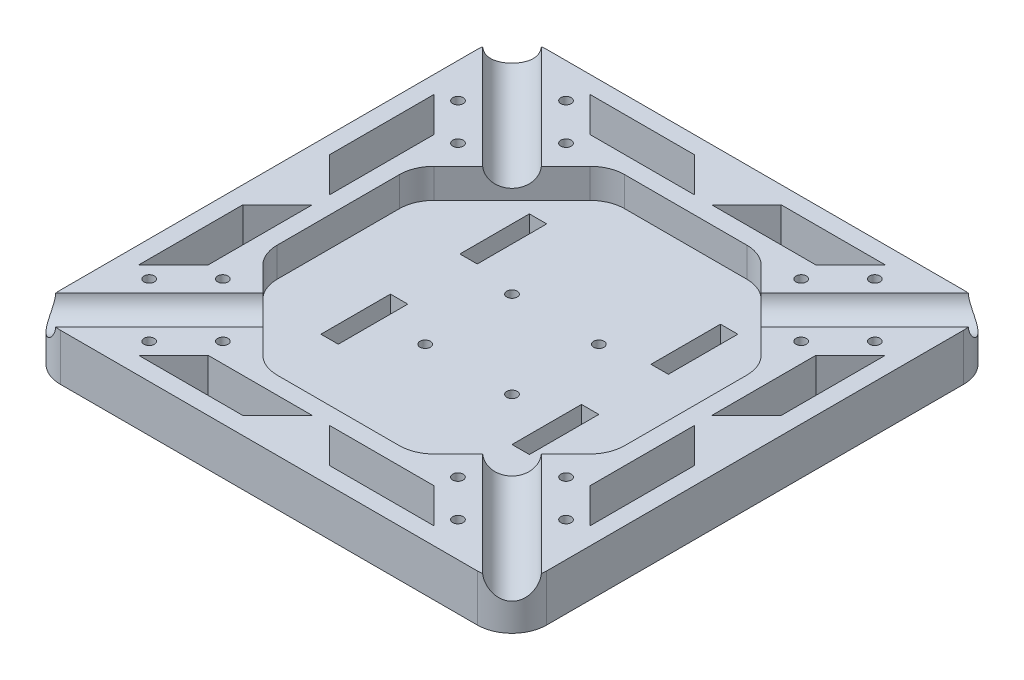
SolidWorks part; units mm, degrees
ref_plane "Plan de face" through (0, 0, 0) normal (0, 0, 1) x (1, 0, 0)
ref_plane "Plan de dessus" through (0, 0, 0) normal (0, 1, 0) x (1, 0, 0)
ref_plane "Plan de droite" through (0, 0, 0) normal (1, 0, 0) x (0, 0, -1)
sketch "Esquisse1" plane through (0, 0, 0) normal (0, 1, 0) x (1, 0, 0)
  line L0 (55, 75.9996) -> (55, -81.4607) construction
  line L1 (-70, 70) -> (70, 70)
  line L2 (-70, 70) -> (-70, -70)
  line L3 (-70, -70) -> (70, -70)
  line L4 (70, 70) -> (70, -70)
  line L6 (-30, 35) -> (-25, 35)
  line L7 (-30, 35) -> (-30, 15)
  line L8 (-30, 15) -> (-25, 15)
  line L9 (65, 75.9996) -> (65, -81.4607) construction
  line L10 (50, 0) -> (70, 0) construction
  line L11 (52.5, 0) -> (65, 12.5) construction
  line L12 (65, 12.5) -> (55, 2.5)
  line L13 (65, -12.5) -> (52.5, 0) construction
  line L14 (65, -12.5) -> (55, -2.5)
  line L15 (65, -12.5) -> (65, -42.5)
  line L16 (65, -42.5) -> (55, -32.5)
  line L17 (55, -32.5) -> (55, -2.5)
  line L18 (65, 12.5) -> (65, 42.5)
  line L19 (65, 42.5) -> (55, 32.5)
  line L20 (55, 32.5) -> (55, 2.5)
  line L21 (12.5, -65) -> (2.5, -55)
  line L22 (-12.5, -65) -> (-2.5, -55)
  line L23 (-12.5, -65) -> (-42.5, -65)
  line L24 (-42.5, -65) -> (-32.5, -55)
  line L25 (-32.5, -55) -> (-2.5, -55)
  line L26 (12.5, -65) -> (42.5, -65)
  line L27 (42.5, -65) -> (32.5, -55)
  line L28 (32.5, -55) -> (2.5, -55)
  line L29 (0, -52.5) -> (12.5, -65) construction
  line L30 (-12.5, -65) -> (0, -52.5) construction
  line L31 (-65, -12.5) -> (-55, -2.5)
  line L32 (-65, 12.5) -> (-55, 2.5)
  line L33 (-65, 12.5) -> (-65, 42.5)
  line L34 (-65, 42.5) -> (-55, 32.5)
  line L35 (-55, 32.5) -> (-55, 2.5)
  line L36 (-65, -12.5) -> (-65, -42.5)
  line L37 (-65, -42.5) -> (-55, -32.5)
  line L38 (-55, -32.5) -> (-55, -2.5)
  line L39 (-52.5, 0) -> (-65, -12.5) construction
  line L40 (-65, 12.5) -> (-52.5, 0) construction
  line L41 (-12.5, 65) -> (-2.5, 55)
  line L42 (12.5, 65) -> (2.5, 55)
  line L43 (12.5, 65) -> (42.5, 65)
  line L44 (42.5, 65) -> (32.5, 55)
  line L45 (32.5, 55) -> (2.5, 55)
  line L46 (-12.5, 65) -> (-42.5, 65)
  line L47 (-42.5, 65) -> (-32.5, 55)
  line L48 (-32.5, 55) -> (-2.5, 55)
  line L49 (0, 52.5) -> (-12.5, 65) construction
  line L50 (12.5, 65) -> (0, 52.5) construction
  line L51 (-25, 35) -> (-25, 15)
  line L52 (-30, -5) -> (-25, -5)
  line L53 (-30, -5) -> (-30, -25)
  line L54 (-30, -25) -> (-25, -25)
  line L55 (-25, -5) -> (-25, -25)
  line L60 (25, 35) -> (30, 35)
  line L61 (25, 35) -> (25, 15)
  line L62 (25, 15) -> (30, 15)
  line L63 (30, 35) -> (30, 15)
  line L64 (25, -5) -> (30, -5)
  line L65 (25, -5) -> (25, -25)
  line L66 (25, -25) -> (30, -25)
  line L67 (30, -5) -> (30, -25)
  dimension "D18" = 20
  dimension "D19" = 5
  dimension "D30" = 20
  dimension "D1" = 140
  dimension "D2" = 140
  dimension "D4" = 20
  dimension "D5" = 20
  dimension "D7" = 5
  dimension "D8" = 5
  dimension "D10" = 5
  dimension "D11" = 2.5
  dimension "D12" = 12.5
  dimension "D13" = 30
  dimension "D14" = 30
  dimension "D15" = 30
  dimension "D16" = 30
  dimension "D20" = 20
  dimension "D21" = 5
  dimension "D24" = 25
  dimension "D26" = 25
  dimension "D27" = 50
  dimension "D28" = 50
  dimension "D32" = 20
  dimension "D33" = 20
  dimension "D34" = 15
  dimension "D35" = 70
  dimension "D37" = 25
  dimension "D38" = 25
  dimension "D17" = 4
extrude "Boss.-Extru.1" add sketch "Esquisse1" along normal blind 13.5
ref_plane "Plan1" through (0, 0, 0) normal (0.7071, 0, 0.7071) x (0.7071, 0, -0.7071)
sketch "Esquisse4" plane through (0, 13.5, 0) normal (0, 1, 0) x (1, 0, 0)
  line L0 (-70, 70) -> (-70, -70) construction
  line L1 (-50, 50) -> (50, 50) construction
  line L2 (-50, 50) -> (-50, -50) construction
  line L3 (-50, -50) -> (50, -50) construction
  line L4 (50, 50) -> (50, -50) construction
  line L5 (70, 70) -> (-70, 70) construction
  line L6 (-37.6256, -34.0901) -> (-34.0901, -37.6256) construction
  line L7 (37.6256, -34.0901) -> (34.0901, -37.6256) construction
  line L8 (-34.0901, 37.6256) -> (-37.6256, 34.0901) construction
  line L9 (34.0901, 37.6256) -> (37.6256, 34.0901) construction
  line L10 (-21.7157, -50) -> (21.7157, -50)
  line L11 (21.7157, -50) -> (50, -21.7157)
  line L12 (50, -21.7157) -> (50, 21.7157)
  line L13 (50, 21.7157) -> (21.7157, 50)
  line L14 (21.7157, 50) -> (-21.7157, 50)
  line L15 (-21.7157, 50) -> (-50, 21.7157)
  line L16 (-50, 21.7157) -> (-50, -21.7157)
  line L17 (-50, -21.7157) -> (-21.7157, -50)
  dimension "D1" = 100
  dimension "D2" = 100
  dimension "D3" = 20
  dimension "D4" = 20
  dimension "D5" = 20
  dimension "D6" = 20
  dimension "D7" = 20
  dimension "D8" = 20
extrude "Enlèv. mat.-Extru.3" cut sketch "Esquisse4" against normal blind 8.5
sketch "Esquisse2" plane through (0, 0, 0) normal (0.7071, 0, 0.7071) x (0.7071, 0, -0.7071)
  line L0 (99.7696, 14) -> (-97.6372, 14) construction
  line L1 (-6, 14) -> (6, 14)
  arc A0 (-6, 14) -> (6, 14) centre (0, 14) ccw
  dimension "D1" = 14
extrude "Enlèv. mat.-Extru.1" cut sketch "Esquisse2" against normal blind 100 and the other way blind 100
ref_axis "Axe1" through (0, -76.1877, 0) along (0, 1, 0)
pattern_circular "Répétition circulaire1" count 2 every 90 about axis through (0, -76.1877, 0) along (0, 1, 0) of "Enlèv. mat.-Extru.1"
fillet "Congé1" radius 10 12 edges at (-70, 4, -70) (-70, 4, 70) (70, 4, -70) (70, 4, 70) (21.7157, 9.25, -50) (50, 9.25, -21.7157) (50, 9.25, 21.7157) (21.7157, 9.25, 50) (-21.7157, 9.25, 50) (-50, 9.25, 21.7157) (-21.7157, 9.25, -50) (-50, 9.25, -21.7157)
sketch "Esquisse3" plane through (0, 13.5, 0) normal (0, 1, 0) x (-1, 0, 0)
  line L0 (-60, -70) -> (60, -70) construction
  line L2 (33.5465, 33.5465) -> (-33.5465, -33.5465) construction
  line L3 (70, -60) -> (70, 60) construction
  line L4 (60, 70) -> (-60, 70) construction
  circle A0 centre (44.4437, 60) radius 1.5
  circle A1 centre (60, 44.4437) radius 1.5
  circle A2 centre (60, -44.4437) radius 1.5
  circle A3 centre (44.4437, -60) radius 1.5
  circle A4 centre (-44.4437, -60) radius 1.5
  circle A5 centre (-60, -44.4437) radius 1.5
  circle A6 centre (-60, 44.4437) radius 1.5
  circle A7 centre (-44.4437, 60) radius 1.5
  circle A8 centre (49.3934, 33.837) radius 1.5
  circle A9 centre (33.837, 49.3934) radius 1.5
  circle A10 centre (33.837, -49.3934) radius 1.5
  circle A11 centre (49.3934, -33.837) radius 1.5
  circle A12 centre (-49.3934, -33.837) radius 1.5
  circle A13 centre (-33.837, -49.3934) radius 1.5
  circle A14 centre (-33.837, 49.3934) radius 1.5
  circle A15 centre (-49.3934, 33.837) radius 1.5
  circle A16 centre (12.5, -12.5) radius 1.5
  circle A17 centre (-12.5, -12.5) radius 1.5
  circle A18 centre (-12.5, 12.5) radius 1.5
  circle A19 centre (12.5, 12.5) radius 1.5
  dimension "D1" = 3
  dimension "D2" = 3
  dimension "D8" = 3
  dimension "D9" = 3
  dimension "D17" = 3
  dimension "D3" = 10
  dimension "D4" = 10
  dimension "D5" = 11
  dimension "D6" = 11
  dimension "D10" = 11
  dimension "D11" = 11
  dimension "D12" = 15
  dimension "D13" = 15
  dimension "D15" = 57.5
  dimension "D16" = 57.5
  dimension "D7" = 4
  dimension "D14" = 4
extrude "Enlèv. mat.-Extru.2" cut sketch "Esquisse3" against normal blind 13.5
